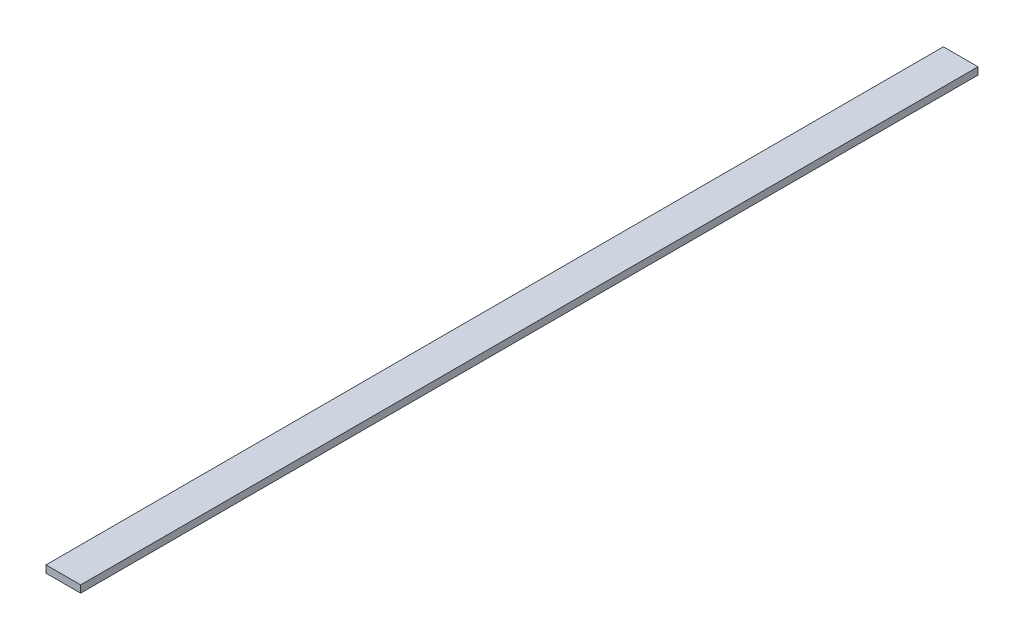
SolidWorks part; units mm, degrees
material "6061 Alloy"
ref_plane "Front Plane" through (0, 0, 0) normal (0, 0, 1) x (1, 0, 0)
ref_plane "Top Plane" through (0, 0, 0) normal (0, 1, 0) x (1, 0, 0)
ref_plane "Right Plane" through (0, 0, 0) normal (1, 0, 0) x (0, 0, -1)
sketch "Sketch1" plane through (0, 0, 0) normal (0, 0, 1) x (1, 0, 0)
  line L0 (6, 2.5) -> (6, 0) construction
  line L1 (0, 0) -> (12, 0)
  line L2 (0, 0) -> (0, 2.5)
  line L3 (0, 2.5) -> (12, 2.5)
  line L4 (12, 0) -> (12, 2.5)
  dimension "D1" = 12
  dimension "D2" = 2.5
extrude "Boss-Extrude1" add sketch "Sketch1" along normal blind 311
sketch "Sketch3" plane through (0, 2.5, 0) normal (0, 1, 0) x (1, 0, 0)
  line L0 (6.323, 0) -> (6.323, -37) construction
  line L1 (12, 0) -> (0, 0) construction
  dimension "D1" = 37
  dimension "D2" = 0
